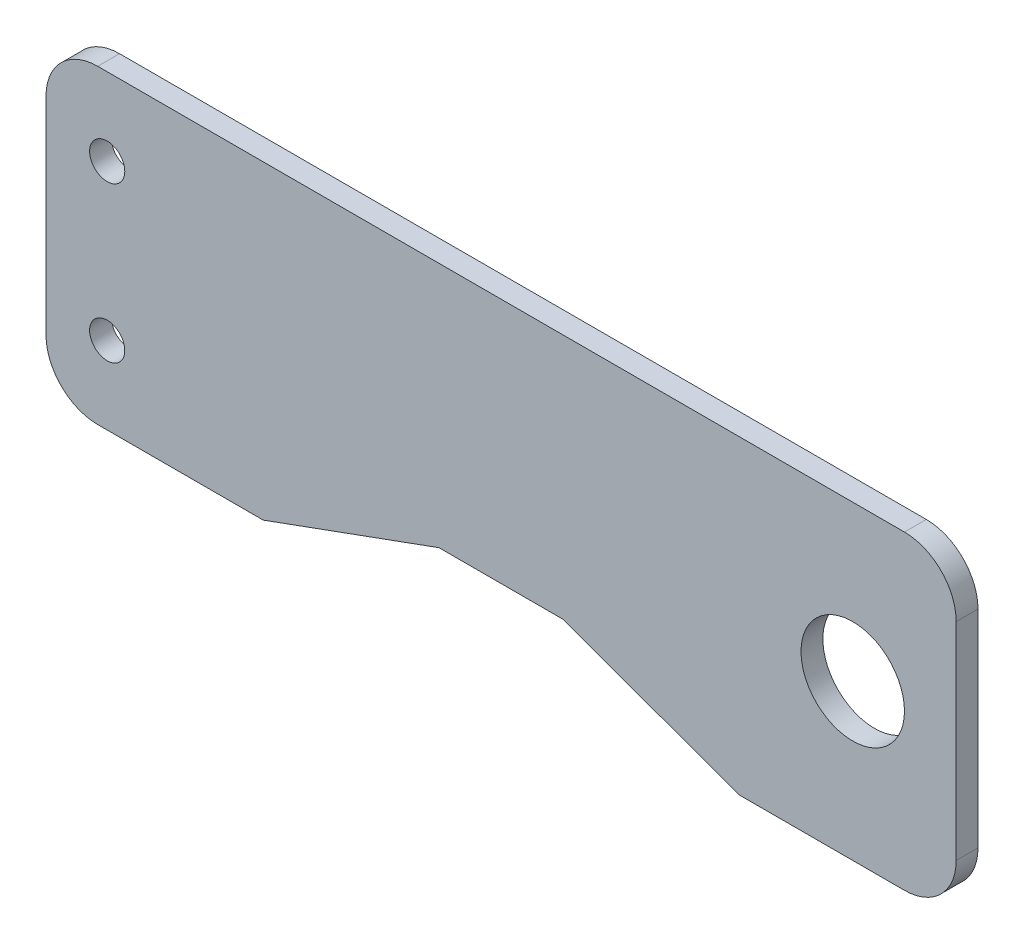
SolidWorks part; units mm, degrees
material "Aluminio 3105"
ref_plane "Alzado" through (0, 0, 0) normal (0, 0, 1) x (1, 0, 0)
ref_plane "Planta" through (0, 0, 0) normal (0, 1, 0) x (1, 0, 0)
ref_plane "Vista lateral" through (0, 0, 0) normal (1, 0, 0) x (0, 0, -1)
sketch "Croquis1" plane through (0, 0, 0) normal (0, 0, 1) x (1, 0, 0)
  line L0 (-7.2912, -21.4058) -> (-7.2912, 8.5942)
  line L5 (80.7088, -21.4058) -> (80.7088, 8.5942)
  line L6 (-49.2912, -6.4058) -> (80.7088, -6.4058) construction
  line L20 (-7.2912, 8.5942) -> (80.7088, 8.5942)
  line L22 (-7.2912, -21.4058) -> (80.7088, -21.4058)
  circle A0 centre (-49.2912, -6.4058) radius 40.5 construction
  circle A1 centre (-49.2912, -6.4058) radius 48.5 construction
  circle A2 centre (-1.3746, 1.0942) radius 1.7
  circle A3 centre (-1.3746, -13.9058) radius 1.7
  point P11 (7.7088, 14.0942)
  point P13 (48.7088, 14.0942)
  point P15 (48.7088, -26.9058)
  point P16 (7.7088, -26.9058)
  dimension "D3" = 130
  dimension "D4" = 81
  dimension "D6" = 15
  dimension "D7" = 3.4
  dimension "D1" = 88
  dimension "D2" = 30
  dimension "D5" = 8
extrude "Saliente-Extruir1" add sketch "Croquis1" along normal blind 2.11
sketch "Croquis6" plane through (0, 0, 2.11) normal (0, 0, 1) x (1, 0, 0)
  line L0 (80.7088, -21.4058) -> (80.7088, 8.5942) construction
  circle A0 centre (70.7088, -6.4058) radius 5
  dimension "D2" = 10
  dimension "D1" = 10
extrude "Cortar-Extruir2" cut sketch "Croquis6" against normal up to surface (2.11 mm away) up to face at (36.7088, -6.4058, 0)
sketch "Croquis7" plane through (0, 0, 2.11) normal (0, 0, 1) x (1, 0, 0)
  line L0 (13.7088, -21.4058) -> (30.7088, -15.2183)
  line L1 (-7.2912, -21.4058) -> (80.7088, -21.4058) construction
  line L2 (30.7088, -15.2183) -> (42.7088, -15.2183)
  line L3 (42.7088, -15.2183) -> (59.7088, -21.4058)
  line L4 (59.7088, -21.4058) -> (13.7088, -21.4058)
  line L5 (-7.2912, -6.4058) -> (80.7088, -6.4058) construction
  line L6 (-7.2912, 8.5942) -> (-7.2912, -21.4058) construction
  line L7 (80.7088, -21.4058) -> (80.7088, 8.5942) construction
  line L8 (36.7088, -6.4058) -> (36.7088, 8.5942) construction
  line L9 (80.7088, 8.5942) -> (-7.2912, 8.5942) construction
  point P16 (36.7088, -15.2183)
  dimension "D1" = 46
  dimension "D2" = 160
  dimension "D3" = 12
extrude "Cortar-Extruir3" cut sketch "Croquis7" against normal up to surface (2.11 mm away) up to face at (75.7088, -6.4058, 0)
fillet "Redondeo1" radius 5 4 edges at (-7.2912, 8.5942, 1.055) (-7.2912, -21.4058, 1.055) (80.7088, 8.5942, 1.055) (80.7088, -21.4058, 1.055)
ref_plane "Plano1" through (0, -6.4058, 0) normal (0, 1, 0) x (1, 0, 0)
